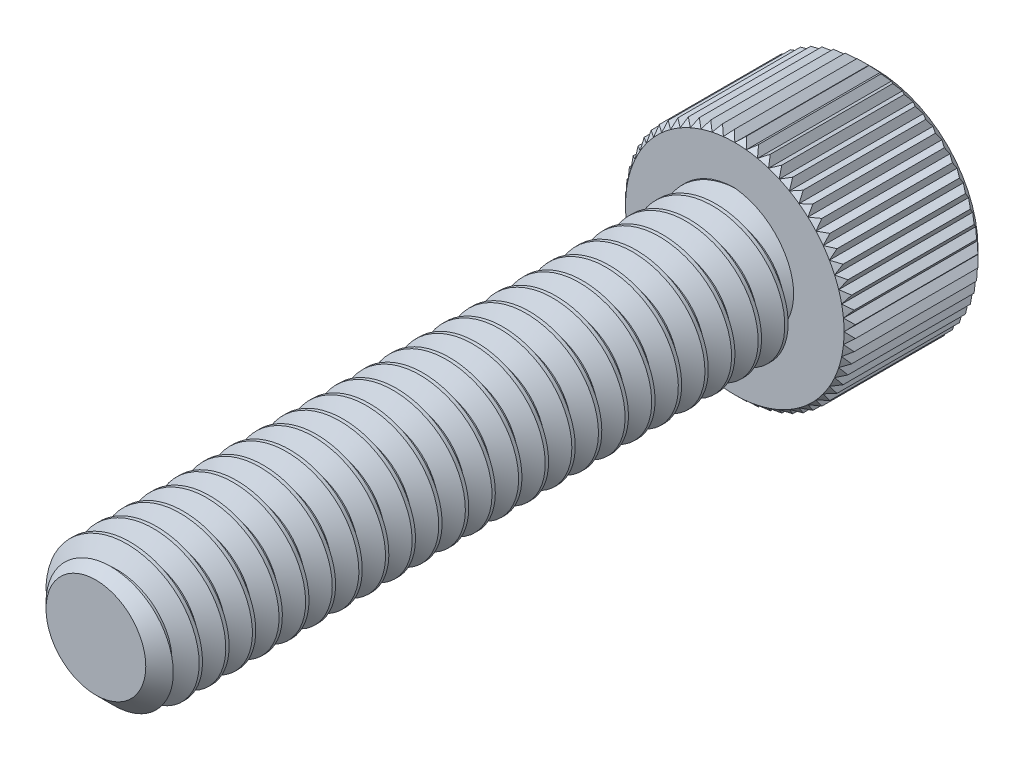
SolidWorks part; units mm, degrees
note: '?' marks a value the reader was unsure of.
ref_plane "Front Plane" through (0, 0, 0) normal (0, 0, 1) x (1, 0, 0)
ref_plane "Top Plane" through (0, 0, 0) normal (0, 1, 0) x (1, 0, 0)
ref_plane "Right Plane" through (0, 0, 0) normal (1, 0, 0) x (0, 0, -1)
sketch "Sketch0" plane through (0, 0, 0) normal (1, 0, 0) x (0, 0, -1)
  line L0 (0, 0) -> (19.05, 0) construction
  point P2 (23.2156, 0)
  point P4 (0, 0)
  dimension "D1" = 19.05
  dimension "D2" = 4.1656
  dimension "Min Thread" = 0
sketch "Sketch1" plane through (0, 0, 0) normal (0, 0, 1) x (1, 0, 0)
  circle A0 centre (0, 0) radius 2.0828
  dimension "OD" = 4.1656
extrude "Extrude1" add sketch "Sketch1" against normal blind 19.05
sketch "Sketch2" plane through (0, 0, 0) normal (0, 0, 1) x (1, 0, 0)
  circle A0 centre (0, 0) radius 2.0828 construction
  circle A1 centre (0, 0) radius 2.0828
curve "Helix/Spiral1" pitch 0.7937 height 19.8438 turns 25 parameters "pitch"=0.7937
chamfer "Chamfer3" distance 0.5953 angle 45 1 edges at (2.0828, 0, 0)
sketch "Sketch3" plane through (0, 0, 0) normal (1, 0, 0) x (0, 0, -1)
  line L0 (-0.6945, 2.0828) -> (-0.3969, 1.5672)
  line L1 (-0.3969, 1.5672) -> (-0.2977, 1.5672)
  line L2 (-0.2977, 1.5672) -> (0, 2.0828)
  line L3 (-0.6945, 2.0828) -> (0, 2.0828)
  line L4 (-0.3473, 2.0828) -> (-0.3473, 1.5672) construction
  line L5 (-0.5457, 1.825) -> (-0.1488, 1.825) construction
  line L6 (0, 2.0828) -> (0, -2.0828) construction
  dimension "D1" = 0.0992
  dimension "D2" = 0.3969
  dimension "D3" = 60
sweep "Cut-Sweep1" cut profiles "Sketch3" path "Helix/Spiral1"
sketch "Sketch5" plane through (0, 0, 0) normal (1, 0, 0) x (0, 0, -1)
  line L0 (19.05, -1.5805) -> (19.05, 1.4861) construction
  line L1 (19.05, 2.0828) -> (0, 2.0828)
  line L2 (19.05, 2.0828) -> (19.05, 0)
  line L3 (19.05, 0) -> (-0.7581, 0)
  line L4 (0, 0) -> (19.05, 0) construction
  line L5 (0, 2.0828) -> (-0.7581, 0)
  line L6 (0, 0) -> (21.59, 0) construction
  dimension "D1" = 70
  dimension "D3" = 2.54
revolve "partially thread" [suppressed] add sketch "Sketch5" angle 360 about L6
sketch "Sketch6" plane through (0, 0, -19.05) normal (0, 0, -1) x (-1, 0, 0)
  circle A0 centre (0, 0) radius 3.429
  dimension "head dia" = 6.858
extrude "Extrude2" add sketch "Sketch6" along normal blind 4.1656
sketch "Sketch7" plane through (0, 0, -23.2156) normal (0, 0, -1) x (-1, 0, 0)
  line L1 (0, 2.0622) -> (-1.7859, 1.0311)
  line L2 (-1.7859, 1.0311) -> (-1.7859, -1.0311)
  line L3 (-1.7859, -1.0311) -> (0, -2.0622)
  line L4 (0, -2.0622) -> (1.7859, -1.0311)
  line L5 (1.7859, -1.0311) -> (1.7859, 1.0311)
  line L6 (1.7859, 1.0311) -> (0, 2.0622)
  circle A0 centre (0, 0) radius 1.7859 construction
  dimension "hex dia" = 3.5719
extrude "Cut-Extrude1" cut sketch "Sketch7" against normal blind 2.6789
sketch "Sketch8" plane through (0, 0, -23.2156) normal (0, 0, -1) x (-1, 0, 0)
  circle A0 centre (0, 0) radius 2.0622
extrude "Cut-Extrude2" cut sketch "Sketch8" against normal through all draft 45
chamfer "Chamfer1" distance 0.3429 angle 45 1 edges at (-3.429, 0, -23.2156)
chamfer "Chamfer2" distance 0.1714 angle 45 1 edges at (-3.429, 0, -19.05)
sketch "Sketch9" plane through (0, 0, 0) normal (1, 0, 0) x (0, 0, -1)
  line L0 (0, 2.0828) -> (0, -2.0828) construction
  line L1 (1.9844, 2.0828) -> (1.9844, -2.0828) construction
  line L2 (23.2156, 3.429) -> (23.2156, -3.429) construction
  line L3 (19.05, 3.429) -> (19.05, -3.429) construction
  line L4 (19.05, 3.2576) -> (19.05, -3.2576) construction
  line L5 (23.2156, -3.0861) -> (23.2156, 3.0861) construction
  line L6 (19.05, -3.429) -> (19.05, 3.429) construction
  line L7 (0, 1.4875) -> (0, -1.4875) construction
  line L8 (-0.6945, 2.0828) -> (0, 2.0828) construction
  line L9 (1.9844, 0) -> (0, 0) construction
  dimension "D1" = 1.9844
sketch "Sketch10" plane through (0, 0, -19.05) normal (0, 0, 1) x (1, 0, 0)
  line L0 (-0.369, 3.6005) -> (0, 3.2576)
  line L1 (0, 3.2576) -> (0.369, 3.6005)
  line L2 (0, 3.2576) -> (0, 3.6005) construction
  line L3 (-0.369, 3.6005) -> (0.369, 3.6005)
  line L4 (0, -3.7667) -> (0, 3.7667) construction
  line L5 (0, 0) -> (0.1795, 3.4243) construction
  line L6 (-0.1795, 3.4243) -> (0, 0) construction
  circle A2 centre (0, 0) radius 3.429 construction
  circle A5 centre (0, 0) radius 3.2576 construction
  dimension "D1" = 6
  dimension "D2" = 0.3429
extrude "Cut-Extrude3" cut sketch "Sketch10" against normal through all
pattern_circular "CirPattern1" count 60 over 360 about axis through (0, 0, 0) along (0, 0, 1) of "Cut-Extrude3"
ref_plane "Contact Plane 1" through (0, 0, -19.05) normal (0, 0, 1) x (1, 0, 0)
ref_axis "Center Axis 1" through (0, 0, 0.8878) along (0, 0, -1)?
equation "\"D3@Helix/Spiral1\" = \"screw length@Extrude1\"+\"pitch@Helix/Spiral1\""
equation "\"D1@Sketch3\" = \"pitch@Helix/Spiral1\"*.125"
equation "\"D2@Sketch3\" = \"pitch@Helix/Spiral1\"*.5"
equation "\"D1@Cut-Extrude1\" = \"hex dia@Sketch7\"*.75"
equation "\"D1@Chamfer1\" = \"head dia@Sketch6\"*.05"
equation "\"D1@Sketch9\" = \"pitch@Helix/Spiral1\"*2.50"
equation "\"D1@Chamfer2\" = \"D1@Chamfer1\"/2"
equation "\"D1@Chamfer3\" = \"pitch@Helix/Spiral1\"*.750"
equation "\"D1@Sketch0\" = \"screw length@Extrude1\""
equation "\"D2@Sketch0\" = \"head depth@Extrude2\""
equation "\"D2@Sketch10\"=\"D1@Chamfer1\""
equation "\"D1@CirPattern1\"=\"D3@CirPattern1\"/\"D1@Sketch10\""
